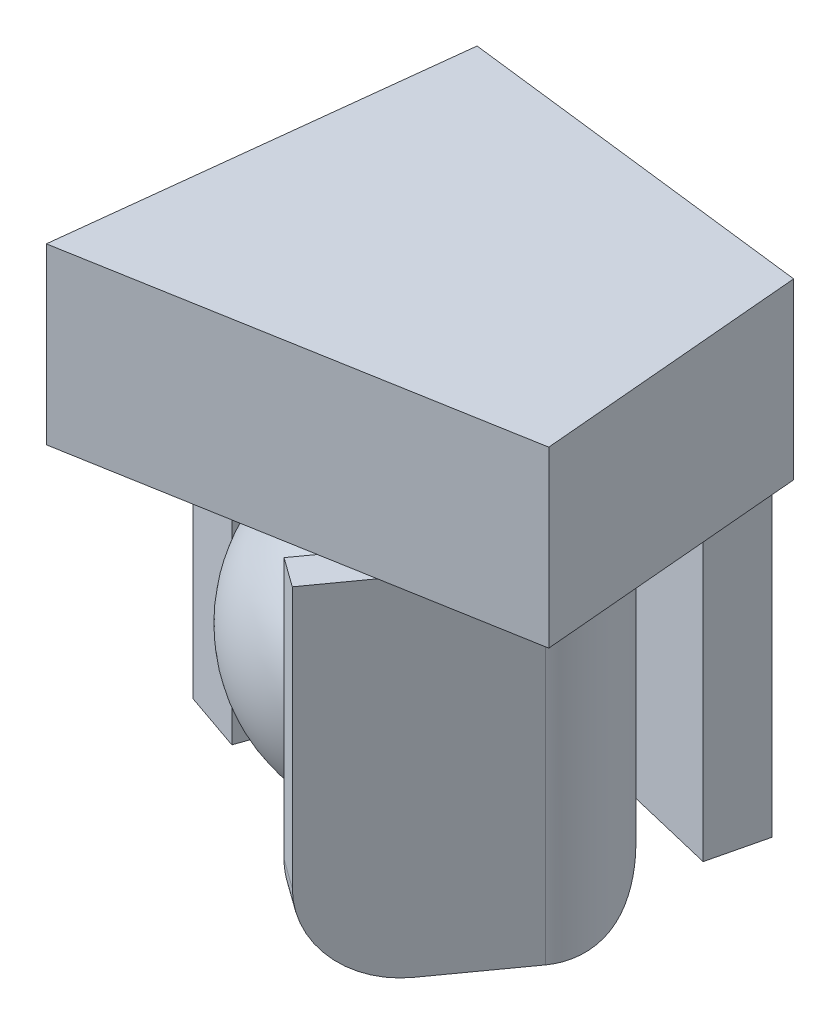
SolidWorks part; units mm, degrees
ref_plane "Front Plane" through (0, 0, 0) normal (0, 0, 1) x (1, 0, 0)
ref_plane "Top Plane" through (0, 0, 0) normal (0, 1, 0) x (1, 0, 0)
ref_plane "Right Plane" through (0, 0, 0) normal (1, 0, 0) x (0, 0, -1)
sketch "Sketch2" plane through (0, 0, 0) normal (0, 0, 1) x (1, 0, 0)
  line L0 (0, 83.9987) -> (0, -83.9987)
  arc A0 (0, 83.9987) -> (0, -83.9987) centre (0, 0) ccw
revolve "Revolve1" add sketch "Sketch2" angle 360 about L0
sketch "Sketch3" plane through (0, 0, 0) normal (0, 0, 1) x (1, 0, 0)
  line L0 (0, 80.7875) -> (0, -80.7875)
  arc A0 (0, 80.7875) -> (0, -80.7875) centre (0, 0) ccw
revolve "Cut-Revolve1" cut sketch "Sketch3" angle 360 about L0
sketch "Sketch4" plane through (0, 0, 0) normal (0, 1, 0) x (1, 0, 0)
  line L0 (112.5477, 11.1027) -> (27.9848, -106.464)
  line L1 (27.9848, -106.464) -> (44.8662, -118.6064)
  line L2 (44.8662, -118.6064) -> (131.2566, 1.501)
  line L3 (131.2566, 1.501) -> (112.5477, 11.1027)
  line L4 (-33.7643, 94.6009) -> (99.6199, 62.6617)
  line L5 (99.6199, 62.6617) -> (107.2678, 94.6009)
  line L6 (107.2678, 94.6009) -> (-30.8746, 121.369)
  line L7 (-30.8746, 121.369) -> (-33.7643, 94.6009)
  line L8 (-66.1598, 65.3993) -> (-93.8404, -14.6008)
  line L9 (-93.8404, -14.6008) -> (-128.1568, -2.7271)
  line L10 (-128.1568, -2.7271) -> (-99.5419, 79.9731)
  line L11 (-99.5419, 79.9731) -> (-66.1598, 65.3993)
  line L12 (-71.1192, 103.5456) -> (-96.426, -118.6064)
  line L13 (-96.426, -118.6064) -> (149.0496, -75.4374)
  line L14 (149.0496, -75.4374) -> (135.6656, 78.6313)
  line L15 (135.6656, 78.6313) -> (-71.1192, 103.5456)
extrude "Boss-Extrude1" add sketch "Sketch4" along normal blind 200 from offset 100 contours L10 L11 L8 L9 | L7 L4 L5 L6 | L0 L1 L2 L3 offset against normal yes
extrude "Boss-Extrude2" add sketch "Sketch4<3>" along normal blind 100 from offset 100 contours L15 L12 L13 L14
sketch "Sketch4<3>" plane through (0, 0, 0) normal (0, 1, 0) x (1, 0, 0) same geometry as "Sketch4"
fillet "Fillet4" radius 50 2 edges at (36.4255, -100, 112.5352) (70.2662, -100, 47.6807)
fillet "Fillet5" radius 50 1 edges at (131.2566, 0, -1.501)
